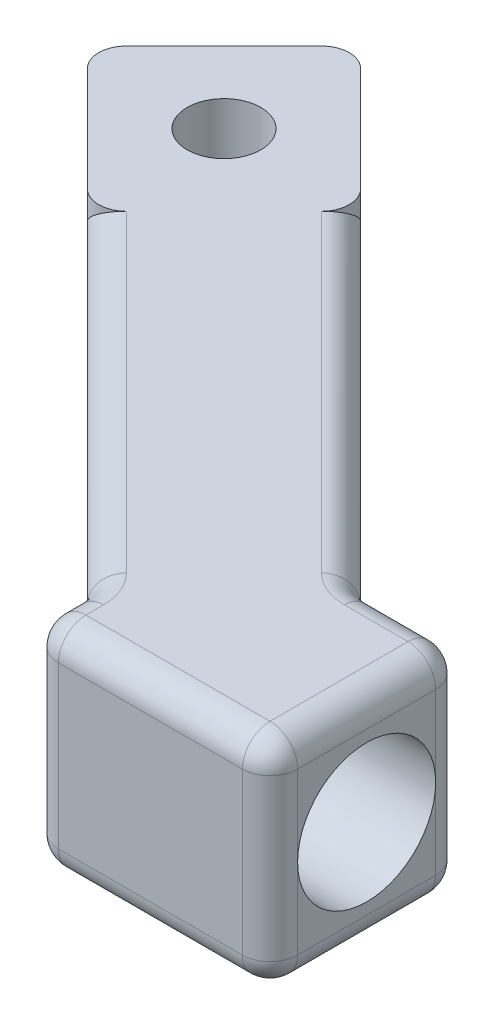
SolidWorks part; units mm, degrees
ref_plane "Front Plane" through (0, 0, 0) normal (0, 0, 1) x (1, 0, 0)
ref_plane "Top Plane" through (0, 0, 0) normal (0, 1, 0) x (1, 0, 0)
ref_plane "Right Plane" through (0, 0, 0) normal (1, 0, 0) x (0, 0, -1)
sketch "Sketch3" plane through (0, 0, 0) normal (0, 1, 0) x (1, 0, 0)
  line L1 (-59.9975, 62.4975) -> (-38.9975, 62.4975)
  line L2 (-59.9975, 62.4975) -> (-59.9975, 36.4975)
  line L3 (-59.9975, 36.4975) -> (-53.8467, 36.4975)
  line L4 (-38.9975, 62.4975) -> (-38.9975, 51.3467)
  line L5 (-59.9975, 62.4975) -> (-38.9975, 36.4975) construction
  line L6 (-59.9975, 36.4975) -> (-38.9975, 62.4975) construction
  line L8 (36.4975, -59.9975) -> (62.4975, -59.9975)
  line L9 (36.4975, -59.9975) -> (36.4975, -53.8467)
  line L10 (51.3467, -38.9975) -> (62.4975, -38.9975)
  line L11 (62.4975, -59.9975) -> (62.4975, -38.9975)
  line L12 (36.4975, -59.9975) -> (62.4975, -38.9975) construction
  line L13 (36.4975, -38.9975) -> (62.4975, -59.9975) construction
  line L14 (-49.4975, 49.4975) -> (49.4975, -49.4975) construction
  line L15 (-98.384, 0) -> (127.6464, 0) construction
  line L16 (-38.9975, 51.3467) -> (51.3467, -38.9975)
  line L18 (36.4975, -53.8467) -> (-53.8467, 36.4975)
  line L19 (36.4975, -38.9975) -> (62.4975, -38.9975) construction
  point P0 (-49.4975, 49.4975)
  point P5 (49.4975, -49.4975)
  point P12 (0, 0)
  dimension "D1" = 140
  dimension "D2" = 26
  dimension "D3" = 26
  dimension "D4" = 21
  dimension "D5" = 21
  dimension "D6" = 45
  dimension "D7" = 21
extrude "Boss-Extrude1" add sketch "Sketch3" along normal blind 37
sketch "Sketch5" plane through (7.8063, 0, -4.5429) normal (-0.7071, 0, 0.7071) x (0.7071, 0, 0.7071)
  line L4 (61.5754, 18.5) -> (-66.1906, 18.5) construction
  line L5 (61.5754, 37) -> (61.5754, 0) construction
  line L6 (61.5754, 37) -> (-66.1906, 37) construction
  line L7 (61.5754, 0) -> (-66.1906, 0) construction
  line L12 (-66.1906, 0) -> (-74.0754, 0) construction
  line L13 (-74.0754, 0) -> (-88.9246, 0) construction
  line L14 (-88.9246, 37) -> (-88.9246, 0) construction
  line L15 (-66.1906, 37) -> (-66.1906, 0) construction
  line L17 (69.4602, 37) -> (61.5754, 37) construction
  line L18 (84.3094, 37) -> (69.4602, 37) construction
  line L19 (84.3094, 37) -> (84.3094, 0) construction
  line L22 (61.5754, 37) -> (12.1924, 37)
  line L23 (-9.8076, 0) -> (-66.1906, 0)
  line L24 (-66.1906, 0) -> (-74.0754, 0)
  line L25 (-74.0754, 0) -> (-88.9246, 0)
  line L26 (-88.9246, 13.5) -> (-88.9246, 0)
  line L29 (69.4602, 37) -> (61.5754, 37)
  line L30 (84.3094, 37) -> (69.4602, 37)
  line L31 (84.3094, 37) -> (84.3094, 23.5)
  line L32 (84.3094, 23.5) -> (12.1924, 23.5)
  line L33 (12.1924, 23.5) -> (12.1924, 37)
  line L34 (-88.9246, 13.5) -> (-9.8076, 13.5)
  line L35 (-9.8076, 13.5) -> (-9.8076, 0)
  line L36 (1.1924, 0) -> (1.1924, 71.3842) construction
  dimension "D1" = 11
  dimension "D2" = 11
  dimension "D3" = 10
  dimension "D4" = 5
extrude "Cut-Extrude1" cut sketch "Sketch5" against normal through all both and the other way through all
sketch "Sketch6" plane through (62.4975, 0, 0) normal (1, 0, 0) x (0, 0, -1)
  line L0 (-49.4975, 11.75) -> (-49.4975, 0) construction
  line L1 (-59.9975, 0) -> (-38.9975, 0) construction
  line L2 (-49.4975, 11.75) -> (-59.9975, 11.75) construction
  line L3 (-59.9975, 23.5) -> (-59.9975, 0) construction
  circle A0 centre (-49.4975, 11.75) radius 7.5
  dimension "D1" = 15
extrude "Cut-Extrude2" cut sketch "Sketch6" against normal through all
sketch "Sketch7" plane through (0, 0, -62.4975) normal (0, 0, -1) x (-1, 0, 0)
  line L0 (49.4975, 25.25) -> (49.4975, 13.5) construction
  line L1 (38.9975, 13.5) -> (59.9975, 13.5) construction
  line L2 (49.4975, 25.25) -> (59.9975, 25.25) construction
  line L3 (59.9975, 37) -> (59.9975, 13.5) construction
  circle A0 centre (49.4975, 25.25) radius 7.5
  dimension "D1" = 15
extrude "Cut-Extrude3" cut sketch "Sketch7" against normal through all
fillet "Fillet1" radius 3 38 edges at (56.9221, 0, 38.9975) (56.9221, 23.5, 38.9975) (-38.9975, 25.25, -51.3467) (26.109, 0, 13.7598) (51.3467, 11.75, 38.9975) (33.8872, 23.5, 21.538) (62.4975, 0, 49.4975) (62.4975, 11.75, 59.9975) (62.4975, 23.5, 49.4975) (62.4975, 11.75, 38.9975) (-6.5533, 0, -4.0533) (-33.9123, 13.5, -16.5631) (-19.0631, 13.5, -31.4123) (-38.9975, 13.5, -56.9221) (-56.9221, 13.5, -36.4975) (-59.9975, 25.25, -36.4975) (-59.9975, 13.5, -49.4975) (-59.9975, 25.25, -62.4975) (-49.4975, 13.5, -62.4975) (-38.9975, 25.25, -62.4975) (-26.1341, 37, -8.7849) (-56.9221, 37, -36.4975) (-59.9975, 37, -49.4975) (-49.4975, 37, -62.4975) (-38.9975, 37, -56.9221) (-11.2849, 37, -23.6341) (9.003, 37, 11.503) (19.038, 23.5, 36.3872) (11.2598, 0, 28.609) (49.4975, 0, 59.9975) (49.4975, 23.5, 59.9975) (36.4975, 11.75, 59.9975) (36.4975, 0, 56.9221) (-53.8467, 16.3199, -36.4975) (-53.8467, 34.1801, -36.4975) (36.4975, 20.6801, 53.8467) (36.4975, 2.8199, 53.8467) (36.4975, 23.5, 56.9221)
sketch "Sketch8" plane through (0, 23.5, 0) normal (0, -1, 0) x (1, 0, 0)
  line L1 (84.3544, 75.3088) -> (-84.3544, 75.3088)
  line L2 (84.3544, 75.3088) -> (84.3544, -75.3088)
  line L3 (84.3544, -75.3088) -> (-84.3544, -75.3088)
  line L4 (-84.3544, 75.3088) -> (-84.3544, -75.3088)
  line L5 (84.3544, 75.3088) -> (-84.3544, -75.3088) construction
  line L6 (84.3544, -75.3088) -> (-84.3544, 75.3088) construction
  point P0 (0, 0)
extrude "Cut-Extrude4" cut sketch "Sketch8" against normal through all
sketch "Sketch9" plane through (-5.3033, 0, -5.3033) normal (-0.7071, 0, -0.7071) x (-0.7071, 0, 0.7071)
  line L1 (-89.3885, 52.5953) -> (93.1144, 52.5953)
  line L2 (-89.3885, 52.5953) -> (-89.3885, -34.4942)
  line L3 (-89.3885, -34.4942) -> (93.1144, -34.4942)
  line L4 (93.1144, 52.5953) -> (93.1144, -34.4942)
  line L5 (-89.3885, 52.5953) -> (93.1144, -34.4942) construction
  line L6 (-89.3885, -34.4942) -> (93.1144, 52.5953) construction
  point P0 (1.863, 9.0505)
extrude "Cut-Extrude5" cut sketch "Sketch9" along normal through all
sketch "Sketch10" plane through (0, 23.5, 0) normal (0, 1, 0) x (1, 0, 0)
  line L0 (8.6495, 3.6997) -> (1.2249, -3.7249) construction
  line L1 (16.4277, -4.0784) -> (0.8713, 11.4779) construction
  line L2 (1.2249, -3.7249) -> (-6.5533, 4.0533) construction
  line L3 (-13.9779, -3.3713) -> (0.8713, 11.4779) construction
  circle A0 centre (1.2249, -3.7249) radius 4
  dimension "D1" = 8
extrude "Cut-Extrude6" cut sketch "Sketch10" against normal through all
fillet "Fillet2" radius 3 6 edges at (-12.7353, 0.8787, 3.3713) (0.8713, 0.8787, -10.2353) (1.5784, 22, 18.9277) (16.4277, 22, 4.0784) (0.8713, 13.25, -11.4779) (-13.9779, 13.25, 3.3713)
equation "\"D2@Sketch3\"=\"D3@Sketch3\""
equation "\"D5@Sketch3\"=\"D4@Sketch3\""
equation "\"D1@Sketch5\"=\"D2@Sketch5\""
equation "\"D4@Sketch5\"=\"D3@Sketch5\"/2"
